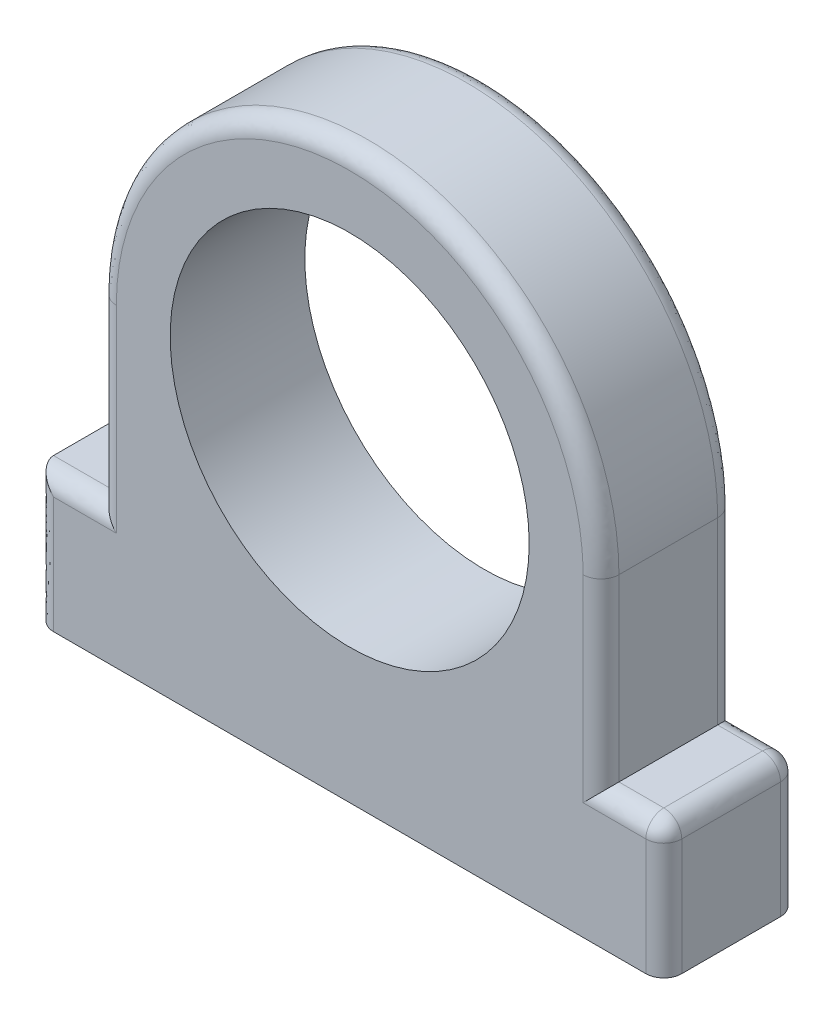
SolidWorks part; units mm, degrees
material "A286 Iron Base Superalloy"
ref_plane "Front Plane" through (0, 0, 0) normal (0, 0, 1) x (1, 0, 0)
ref_plane "Top Plane" through (0, 0, 0) normal (0, 1, 0) x (1, 0, 0)
ref_plane "Right Plane" through (0, 0, 0) normal (1, 0, 0) x (0, 0, -1)
sketch "Sketch1" plane through (0, 0, 0) normal (0, 0, 1) x (1, 0, 0)
  line L0 (-23.7457, -15) -> (46.2543, -15)
  line L1 (46.2543, -15) -> (46.2543, 0)
  line L2 (46.2543, 0) -> (39.2543, 0)
  line L3 (-23.7457, -15) -> (-23.7457, 0)
  line L4 (-23.7457, 0) -> (-16.7457, 0)
  line L5 (-16.7457, 0) -> (-16.7457, 20)
  line L6 (39.2543, 0) -> (39.2543, 20)
  arc A0 (-16.7457, 20) -> (39.2543, 20) centre (11.2543, 20) cw
  circle A1 centre (11.2543, 20) radius 20
  dimension "D4" = 40
  dimension "D1" = 70
  dimension "D2" = 7
  dimension "D3" = 15
  dimension "D5" = 20
extrude "Boss-Extrude1" add sketch "Sketch1" along normal blind 15
fillet "Fillet1" radius 2 15 edges at (46.2543, -7.5, 15) (46.2543, -7.5, 0) (46.2543, 0, 7.5) (42.7543, 0, 0) (-20.2457, 0, 0) (-23.7457, -7.5, 0) (39.2543, 10, 0) (-16.7457, 10, 0) (11.2543, 48, 0) (-23.7457, -7.5, 15) (-20.2457, 0, 15) (42.7543, 0, 15) (39.2543, 10, 15) (-16.7457, 10, 15) (11.2543, 48, 15) first distance on face at (46.2543, -7.5, 7.5) first distance on face at (42.7543, 0, 7.5) first distance on face at (-20.2457, 0, 7.5) first distance on face at (-23.7457, -7.5, 7.5) first distance on face at (39.2543, 10, 7.5) first distance on face at (-16.7457, 10, 7.5) first distance on face at (11.2543, 34, 7.5)
